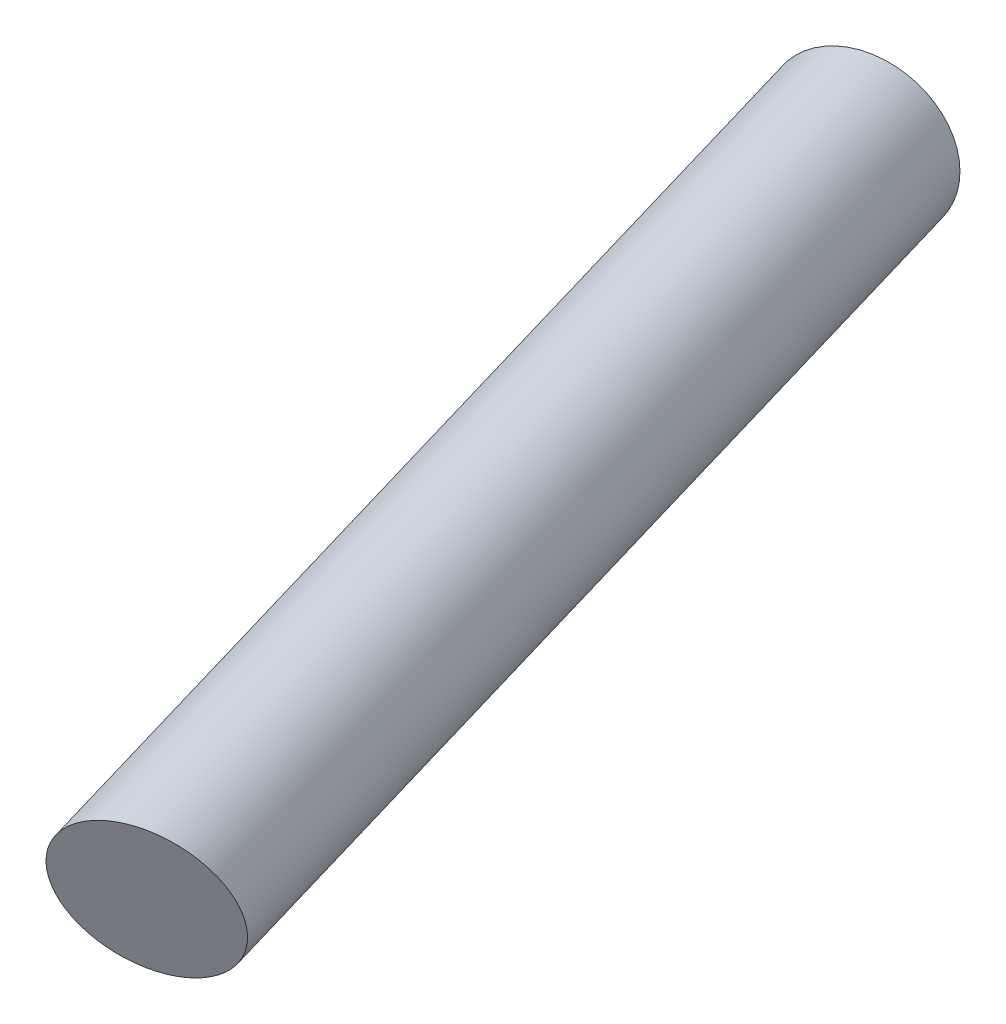
SolidWorks part; units mm, degrees
ref_plane "Front Plane" through (0, 0, 0) normal (0, 0, 1) x (1, 0, 0)
ref_plane "Top Plane" through (0, 0, 0) normal (0, 1, 0) x (1, 0, 0)
ref_plane "Right Plane" through (0, 0, 0) normal (1, 0, 0) x (0, 0, -1)
ref_plane "Plane1" through (-82.3648, -121.2062, -6) normal (0.2822, 0, 0.9594) x (0.9594, 0, -0.2822)
sketch "Sketch2" plane through (-82.3648, -121.2062, -6) normal (0.2822, 0, 0.9594) x (0.9594, 0, -0.2822)
  circle A0 centre (0, 0) radius 4.75
  dimension "D1" = 9.5
extrude "Boss-Extrude1" add sketch "Sketch2" against normal blind 57
sketch "Sketch3" plane through (-8.1819, 0, -27.8185) normal (0.2822, 0, 0.9594) x (0.9594, 0, -0.2822)
  circle A1 centre (-77.325, -121.2062) radius 4.75
  circle A2 centre (-77.325, -121.2062) radius 4.75
  dimension "D1" = 0
extrude "Boss-Extrude2" add sketch "Sketch3" along normal blind 8
sketch "Sketch4" plane through (-99.5395, -19.11, 29.2763) normal (-0.9435, -0.1811, 0.2775) x (0.2725, 0.0523, 0.9607)
  line L1 (-31.0636, -114.9917) -> (-9.4313, -53.697)
  line L2 (-9.4313, -53.697) -> (-24.5185, -117.1523)
  line L3 (-24.5185, -117.1523) -> (-31.0636, -114.9917)
extrude "Cut-Extrude1" cut sketch "Sketch4" against normal through all
other "DeleteFace1" face at (-80.6932, -117.8912, 1.8472) and patch yes
